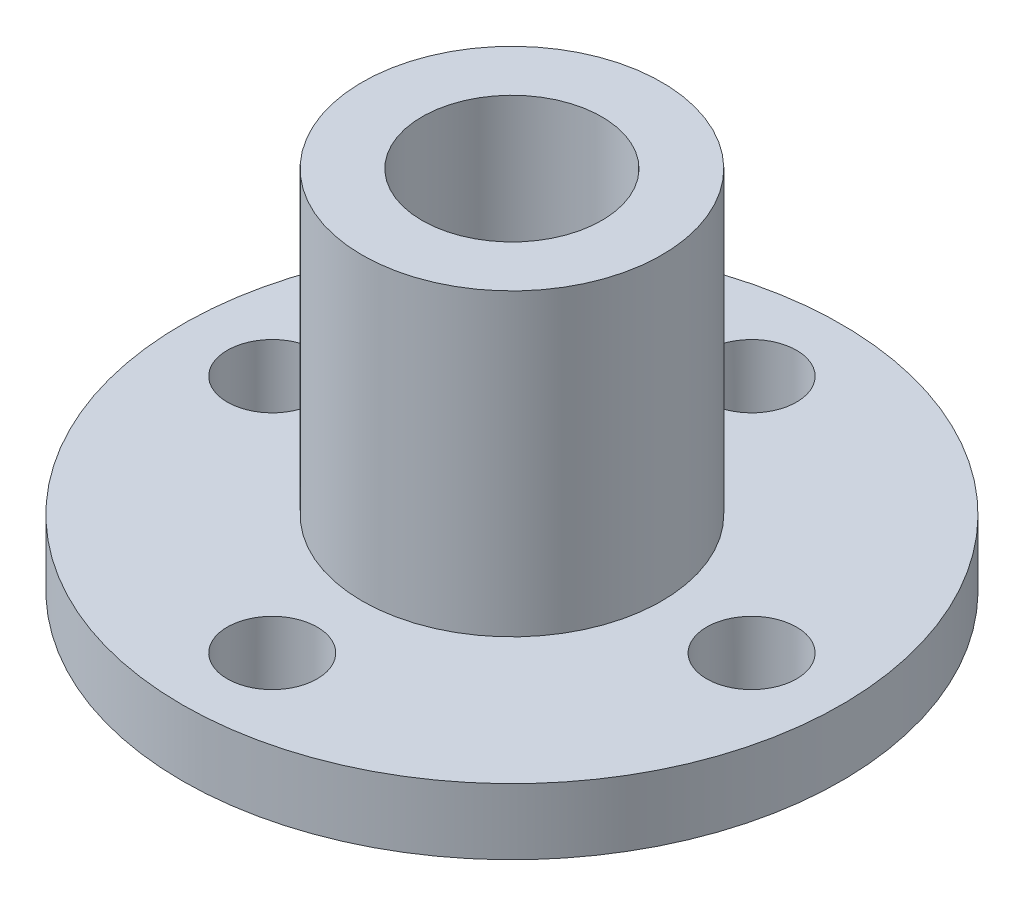
SolidWorks part; units mm, degrees
ref_plane "前视基准面" through (0, 0, 0) normal (0, 0, 1) x (1, 0, 0)
ref_plane "上视基准面" through (0, 0, 0) normal (0, 1, 0) x (1, 0, 0)
ref_plane "右视基准面" through (0, 0, 0) normal (1, 0, 0) x (0, 0, -1)
other "Configuration Table"
sketch "草图1" plane through (0, 0, 0) normal (0, 1, 0) x (1, 0, 0)
  circle A0 centre (0, 0) radius 11
  dimension "D1" = 22
extrude "凸台-拉伸1" add sketch "草图1" along normal blind 2.2
sketch "草图2" plane through (0, 2.2, 0) normal (0, 1, 0) x (1, 0, 0)
  circle A0 centre (0, 0) radius 5
  dimension "D1" = 10
extrude "凸台-拉伸2" add sketch "草图2" along normal blind 10
sketch "草图3" plane through (0, 12.2, 0) normal (0, 1, 0) x (1, 0, 0)
  circle A1 centre (0, 0) radius 3
  dimension "D1" = 6
extrude "切除-拉伸1" cut sketch "草图3" against normal blind 15
sketch "草图4" plane through (0, 0, 0) normal (0, 0, 1) x (1, 0, 0)
  line L0 (11, 2.2) -> (-11, 2.2) construction
  circle A0 centre (0, 7.2) radius 1.5
  point P4 (0, 0)
  dimension "D1" = 3
  dimension "D2" = 5
extrude "切除-拉伸2" cut sketch "草图4" against normal blind 15
sketch "草图5" plane through (0, 2.2, 0) normal (0, 1, 0) x (1, 0, 0)
  circle A0 centre (-8, 0) radius 1.5
  point P2 (0, 0)
  dimension "D1" = 3
  dimension "D2" = 8
extrude "切除-拉伸3" cut sketch "草图5" against normal blind 15
ref_axis "基准轴1" through (0, 12.2, 0) along (0, -1, 0)
pattern_circular "阵列(圆周)1" count 4 over 360 about axis through (0, 12.2, 0) along (0, -1, 0) of "切除-拉伸3"
